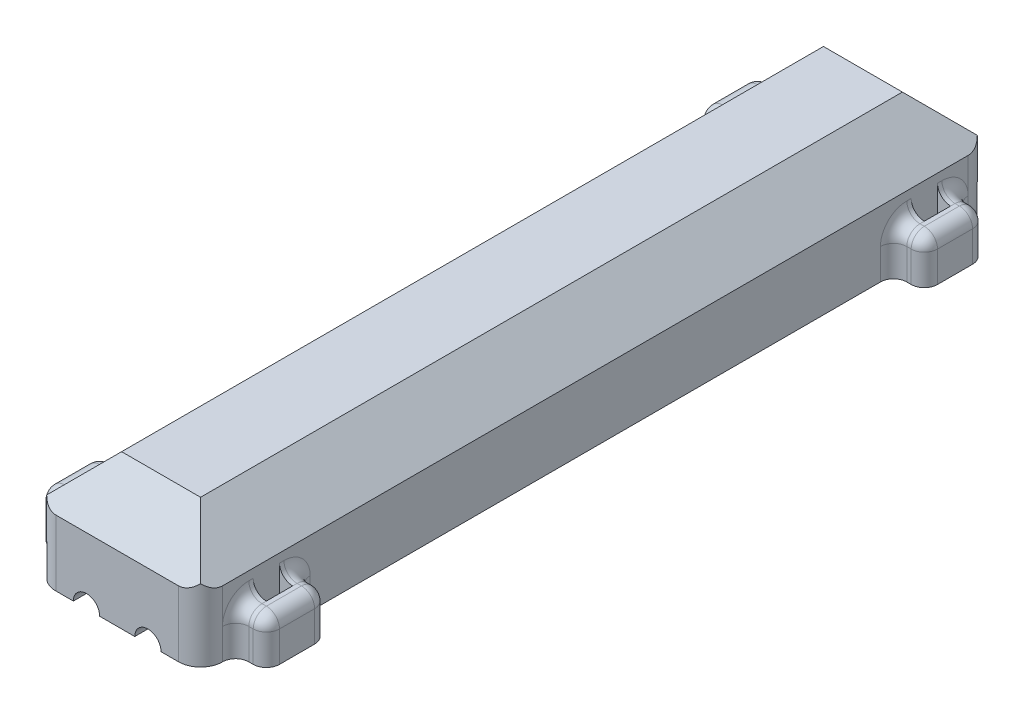
SolidWorks part; units mm, degrees
ref_plane "Front Plane" through (0, 0, 0) normal (0, 0, 1) x (1, 0, 0)
ref_plane "Top Plane" through (0, 0, 0) normal (0, 1, 0) x (1, 0, 0)
ref_plane "Right Plane" through (0, 0, 0) normal (1, 0, 0) x (0, 0, -1)
sketch "Sketch1" plane through (0, 0, 0) normal (0, 1, 0) x (1, 0, 0)
  line L1 (-19, -90) -> (19, -90)
  line L2 (-19, -90) -> (-19, 90)
  line L3 (-19, 90) -> (19, 90)
  line L4 (19, -90) -> (19, 90)
  line L5 (-19, -90) -> (19, 90) construction
  line L6 (-19, 90) -> (19, -90) construction
  point P0 (0, 0)
  dimension "D1" = 180
  dimension "D2" = 38
extrude "Boss-Extrude1" add sketch "Sketch1" along normal blind 25
sketch "Sketch2" plane through (0, 0, 0) normal (0, -1, 0) x (1, 0, 0)
  line L1 (-16, -87) -> (16, -87)
  line L2 (-16, -87) -> (-16, 87)
  line L3 (-16, 87) -> (16, 87)
  line L4 (16, -87) -> (16, 87)
  line L5 (-16, -87) -> (16, 87) construction
  line L6 (-16, 87) -> (16, -87) construction
  point P0 (0, 0)
  dimension "D1" = 32
  dimension "D2" = 174
extrude "Cut-Extrude1" cut sketch "Sketch2" against normal blind 22
chamfer "Chamfer1" distance 10 angle 45 8 edges at (0, 25, 90) (-19, 25, 0) (19, 25, 0) (0, 25, -90) (0, 22, -87) (-16, 22, 0) (0, 22, 87) (16, 22, 0)
fillet "Fillet1" radius 5 4 edges at (-19, 7.5, -90) (19, 7.5, -90) (-19, 7.5, 90) (19, 7.5, 90)
fillet "Fillet2" radius 2 4 edges at (-16, 6, -87) (16, 6, -87) (16, 6, 87) (-16, 6, 87)
sketch "Sketch3" plane through (19, 0, 0) normal (1, 0, 0) x (0, 0, -1)
  line L0 (-85, 0) -> (85, 0) construction
  line L1 (-68, 10) -> (-82, 10)
  line L2 (-68, 10) -> (-68, 0)
  line L3 (-68, 0) -> (-82, 0)
  line L4 (-82, 10) -> (-82, 0)
  line L5 (-68, 10) -> (-82, 0) construction
  line L6 (-68, 0) -> (-82, 10) construction
  line L7 (-85, 15) -> (-85, 0) construction
  line L8 (0, 0) -> (0, 15) construction
  line L9 (85, 15) -> (-85, 15) construction
  line L10 (68, 0) -> (82, 0)
  line L11 (82, 10) -> (82, 0)
  line L12 (68, 0) -> (82, 10) construction
  line L13 (68, 10) -> (82, 0) construction
  line L14 (68, 10) -> (68, 0)
  line L15 (68, 10) -> (82, 10)
  point P0 (-75, 5)
  point P18 (75, 5)
  dimension "D1" = 3
  dimension "D2" = 14
  dimension "D3" = 10
extrude "Boss-Extrude2" add sketch "Sketch3" along normal blind 7
sketch "Sketch4" plane through (-19, 0, 0) normal (-1, 0, 0) x (0, 0, 1)
  line L0 (-85, 0) -> (85, 0) construction
  line L1 (-68, 10.9395) -> (-82, 10.9395)
  line L2 (-68, 10.9395) -> (-68, 0)
  line L3 (-68, 0) -> (-82, 0)
  line L4 (-82, 10.9395) -> (-82, 0)
  line L5 (-68, 10.9395) -> (-82, 0) construction
  line L6 (-68, 0) -> (-82, 10.9395) construction
  line L7 (-85, 15) -> (-85, 0) construction
  line L8 (0, 15) -> (0, 0) construction
  line L9 (85, 15) -> (-85, 15) construction
  line L10 (68, 0) -> (82, 10.9395) construction
  line L11 (68, 10.9395) -> (82, 0) construction
  line L12 (82, 10.9395) -> (82, 0)
  line L13 (68, 0) -> (82, 0)
  line L14 (68, 10.9395) -> (68, 0)
  line L15 (68, 10.9395) -> (82, 10.9395)
  point P0 (-75, 5.4697)
  point P18 (75, 5.4697)
  dimension "D1" = 3
  dimension "D2" = 14
  dimension "D3" = 10.9395
extrude "Boss-Extrude3" add sketch "Sketch4" along normal blind 7
fillet "Fillet3" radius 3 32 edges at (-26, 5.4697, 82) (-26, 10.9395, 75) (-26, 5.4697, 68) (-26, 5.4697, -68) (-26, 10.9395, -75) (-26, 5.4697, -82) (26, 10, -75) (26, 5, -82) (26, 5, -68) (26, 5, 68) (26, 10, 75) (26, 5, 82) (22.5, 10, -82) (22.5, 10, -68) (22.5, 10, 68) (22.5, 10, 82) (-22.5, 10.9395, 82) (-22.5, 10.9395, 68) (-22.5, 10.9395, -68) (-22.5, 10.9395, -82) (19, 5, 68) (19, 5, 82) (19, 5, -82) (19, 5, -68) (-19, 5.4697, 82) (-19, 5.4697, 68) (-19, 5.4697, -68) (-19, 5.4697, -82) (19, 10, 75) (19, 10, -75) (-19, 10.9395, 75) (-19, 10.9395, -75)
sketch "Sketch5" plane through (0, 0, 0) normal (0, -1, 0) x (1, 0, 0)
  line L5 (0, 90) -> (0, 0) construction
  line L6 (-14, 90) -> (14, 90) construction
  line L7 (-19, 0) -> (19, 0) construction
  line L8 (-19, -65) -> (-19, 65) construction
  line L9 (19, 65) -> (19, -65) construction
  line L22 (22, 72) -> (19, 72)
  line L23 (19, 78) -> (19, 72)
  line L24 (22, 78) -> (19, 78)
  line L25 (22, 78) -> (22, 72)
  line L26 (-22, -72) -> (-19, -72)
  line L27 (-19, -78) -> (-19, -72)
  line L28 (-22, -78) -> (-19, -78)
  line L29 (-22, -78) -> (-22, -72)
  line L30 (22, -78) -> (22, -72)
  line L39 (-23, 82) -> (-22, 82) construction
  line L40 (-22, 78) -> (-19, 78)
  line L41 (-22, 78) -> (-22, 72)
  line L42 (-22, 72) -> (-19, 72)
  line L43 (-19, 78) -> (-19, 72)
  line L44 (22, -78) -> (19, -78)
  line L45 (19, -78) -> (19, -72)
  line L46 (22, -72) -> (19, -72)
  dimension "D1" = 4
  dimension "D2" = 3
  dimension "D3" = 6
extrude "Cut-Extrude2" cut sketch "Sketch5" against normal through all
sketch "Sketch6" plane through (0, 0, 90) normal (0, 0, 1) x (1, 0, 0)
  line L0 (-14, 0) -> (14, 0) construction
  line L1 (0, 3.4835) -> (0, -2.5043) construction
  circle A1 centre (-7, 0) radius 3
  circle A2 centre (7, 0) radius 3
  dimension "D1" = 6
  dimension "D2" = 7
extrude "Cut-Extrude3" cut sketch "Sketch6" against normal blind 10
